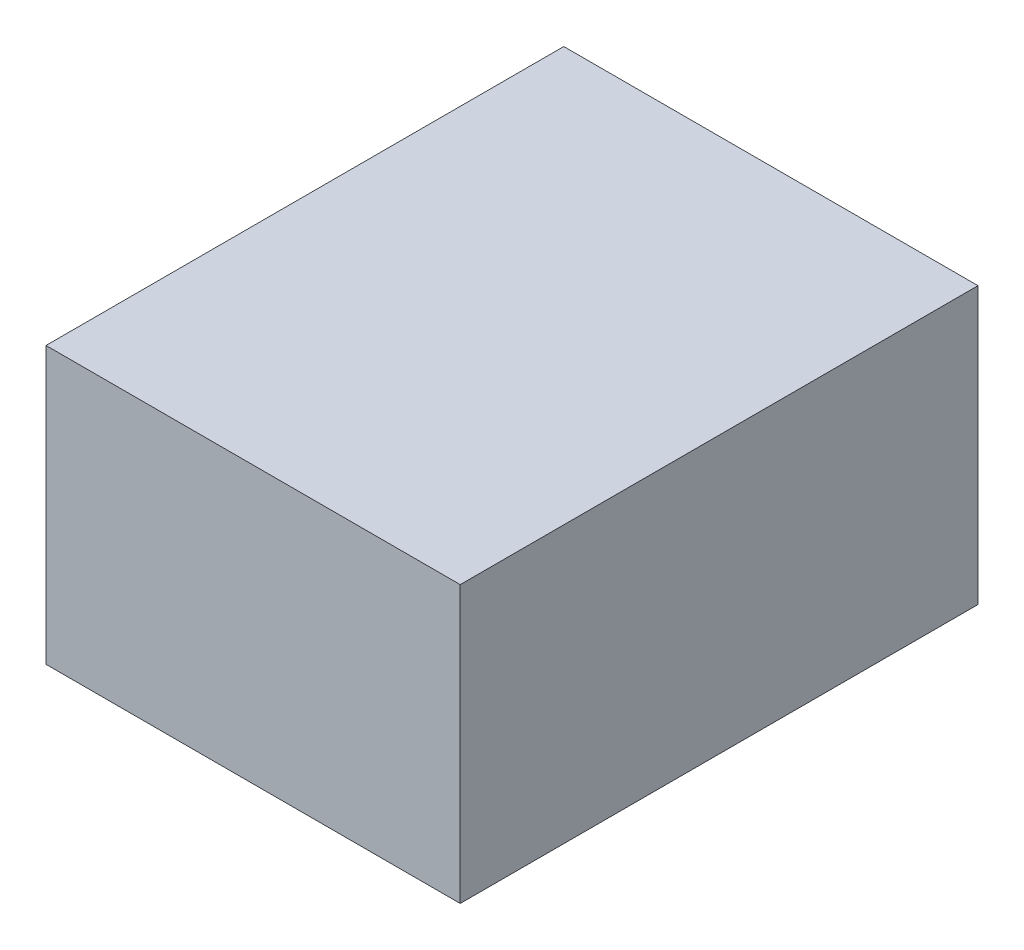
SolidWorks part; units mm, degrees
ref_plane "Front Plane" through (0, 0, 0) normal (0, 0, 1) x (1, 0, 0)
ref_plane "Top Plane" through (0, 0, 0) normal (0, 1, 0) x (1, 0, 0)
ref_plane "Right Plane" through (0, 0, 0) normal (1, 0, 0) x (0, 0, -1)
sketch "Sketch1" plane through (0, 0, 0) normal (0, 0, 1) x (1, 0, 0)
  line L1 (0, 0) -> (304.8, 0)
  line L2 (0, 0) -> (0, 203.2)
  line L3 (0, 203.2) -> (304.8, 203.2)
  line L4 (304.8, 0) -> (304.8, 203.2)
  dimension "D1" = 203.2
  dimension "D2" = 304.8
extrude "Boss-Extrude1" add sketch "Sketch1" along normal mid plane 381
sketch "Sketch2" plane through (0, 0, 0) normal (0, 0, 1) x (1, 0, 0)
  point P0 (-500.7439, 114.7555)
ref_axis "Axis1" through (-500.7439, 114.7555, 0) along (0, 0, 1)
